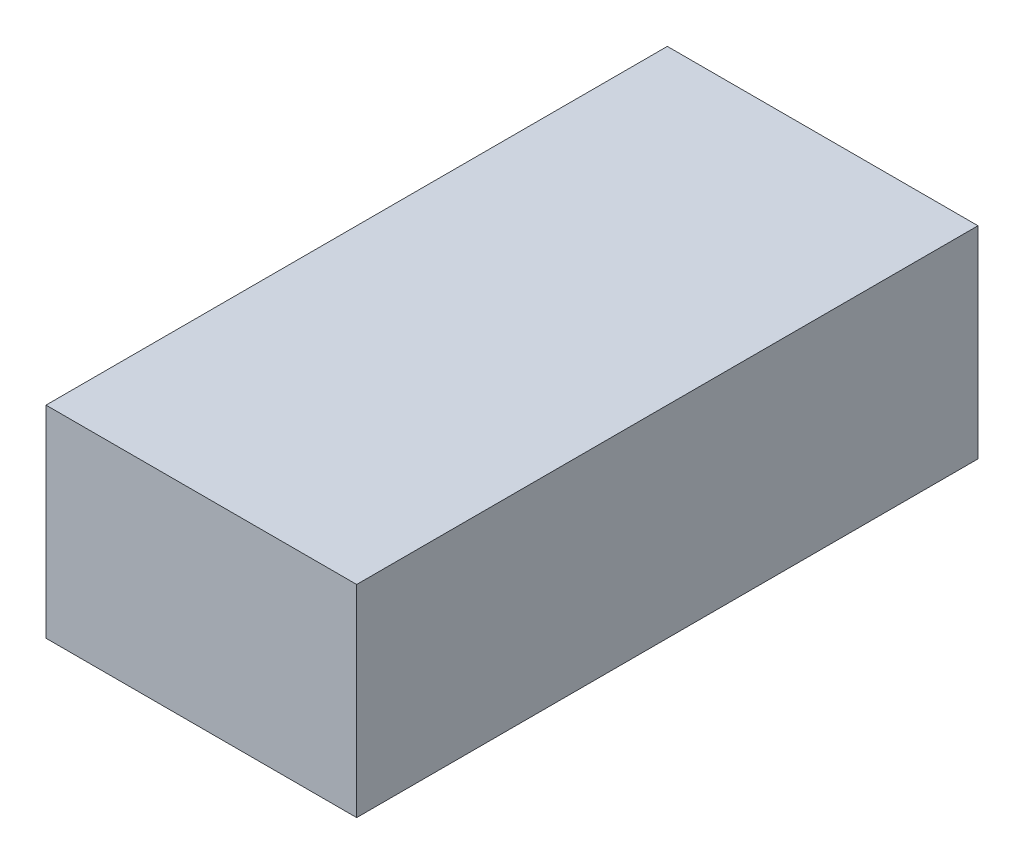
SolidWorks part; units mm, degrees
ref_plane "Front Plane" through (0, 0, 0) normal (0, 0, 1) x (1, 0, 0)
ref_plane "Top Plane" through (0, 0, 0) normal (0, 1, 0) x (1, 0, 0)
ref_plane "Right Plane" through (0, 0, 0) normal (1, 0, 0) x (0, 0, -1)
sketch "Sketch1" plane through (0, 0, 0) normal (0, 1, 0) x (1, 0, 0)
  line L1 (0, 200) -> (100, 200)
  line L2 (0, 200) -> (0, 0)
  line L3 (0, 0) -> (100, 0)
  line L4 (100, 200) -> (100, 0)
  point P4 (-70, -40)
  point P6 (0, 0)
  dimension "D1" = 100
  dimension "D2" = 200
extrude "Boss-Extrude1" add sketch "Sketch1" along normal blind 65 contours L4 L1 L2 L3 region at (50, 0, -100)
